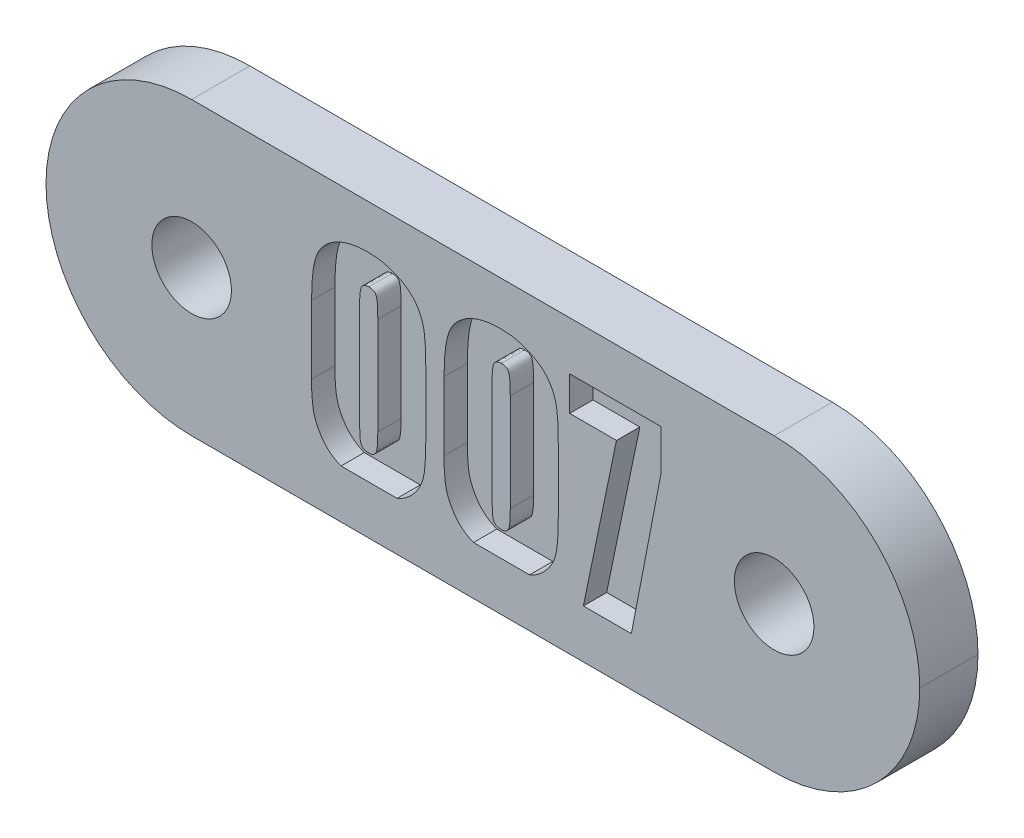
SolidWorks part; units mm, degrees
ref_plane "Front Plane" through (0, 0, 0) normal (0, 0, 1) x (1, 0, 0)
ref_plane "Top Plane" through (0, 0, 0) normal (0, 1, 0) x (1, 0, 0)
ref_plane "Right Plane" through (0, 0, 0) normal (1, 0, 0) x (0, 0, -1)
sketch "Sketch1" plane through (0, 0, 0) normal (0, 0, 1) x (1, 0, 0)
  line L1 (-22.5, 7.5) -> (22.5, 7.5)
  line L2 (-22.5, 7.5) -> (-22.5, -7.5)
  line L3 (-22.5, -7.5) -> (22.5, -7.5)
  line L4 (22.5, 7.5) -> (22.5, -7.5)
  line L5 (-22.5, 7.5) -> (22.5, -7.5) construction
  line L6 (-22.5, -7.5) -> (22.5, 7.5) construction
  point P0 (0, 0)
  dimension "D1" = 45
  dimension "D2" = 15
extrude "Boss-Extrude1" add sketch "Sketch1" along normal blind 3
sketch "Sketch2" plane through (0, 0, 3) normal (0, 0, 1) x (1, 0, 0)
  circle A0 centre (15, 0) radius 2.05
  circle A1 centre (-15, 0) radius 2.05
  point P4 (13.7306, -0.519)
  dimension "D1" = 4.1
  dimension "D2" = 30
  dimension "D3" = 15
extrude "Cut-Extrude1" cut sketch "Sketch2" against normal blind 4
sketch "Sketch5" plane through (0, 0, 3) normal (0, 0, 1) x (1, 0, 0)
  line L0 (-11, -5) -> (11, -5)
  line L2 (-2.9412, 1.6287) -> (-2.9412, -1.7353)
  line L3 (-8.8235, -1.8897) -> (-8.8235, 1.6287)
  line L4 (-6.3529, 2.4908) -> (-6.3529, -2.4596)
  line L5 (-5.4118, -2.5349) -> (-5.4118, 2.4908)
  line L6 (3.8824, 1.6287) -> (3.8824, -1.7353)
  line L7 (-2, -1.8897) -> (-2, 1.6287)
  line L8 (0.4706, 2.4908) -> (0.4706, -2.4596)
  line L9 (1.4118, -2.5349) -> (1.4118, 2.4908)
  line L10 (9.1765, 5) -> (9.1765, 2.9118)
  line L11 (9.1765, 2.9118) -> (7.6471, -5)
  line L12 (7.6471, -5) -> (5.1765, -5)
  line L13 (5.1765, -5) -> (6.8824, 3.2353)
  line L14 (6.8824, 3.2353) -> (4.4706, 3.2353)
  line L15 (4.4706, 3.2353) -> (4.4706, 5)
  line L16 (4.4706, 5) -> (9.1765, 5)
  spline S0 degree 3 poles (-2.9412, -1.7353) (-2.9408, -1.913) (-2.9449, -2.1704) (-2.9557, -2.5002) (-2.9722, -2.7188) (-2.9863, -2.9177) (-3.0101, -3.097) (-3.0323, -3.2575) (-3.0712, -3.4455) (-3.1387, -3.6644) (-3.2499, -3.9155) (-3.3966, -4.1568) (-3.5737, -4.386) (-3.7748, -4.5972) (-4.0023, -4.7766) (-4.2476, -4.9275) (-4.515, -5.043) (-4.7995, -5.1277) (-5.2075, -5.2144) (-5.5264, -5.2336) (-5.7426, -5.2353) knots 0 0 0 0 0.102604 0.148628 0.190468 0.22916 0.263737 0.294856 0.322678 0.374488 0.426751 0.480869 0.537122 0.593665 0.648803 0.703893 0.759497 0.816458 0.875017 1 1 1 1
  spline S1 degree 3 poles (-5.7426, -5.2353) (-6.0162, -5.2337) (-6.4114, -5.2176) (-6.9066, -5.1245) (-7.2265, -5.0367) (-7.5117, -4.9165) (-7.7642, -4.7655) (-7.99, -4.5892) (-8.1798, -4.3809) (-8.3418, -4.1579) (-8.4785, -3.9256) (-8.5935, -3.6898) (-8.6671, -3.4841) (-8.7147, -3.3088) (-8.7423, -3.1586) (-8.7689, -2.9908) (-8.7878, -2.8054) (-8.8052, -2.602) (-8.8188, -2.2949) (-8.825, -2.0552) (-8.8235, -1.8897) knots 0 0 0 0 0.15504 0.222773 0.284785 0.342425 0.397312 0.450868 0.503863 0.556225 0.606593 0.65622 0.704478 0.729962 0.758931 0.790855 0.826083 0.864351 0.906358 1 1 1 1
  spline S2 degree 3 poles (-8.8235, 1.6287) (-8.8236, 1.8457) (-8.8173, 2.1609) (-8.7927, 2.5659) (-8.7667, 2.8375) (-8.7353, 3.0869) (-8.6918, 3.314) (-8.6454, 3.52) (-8.5898, 3.707) (-8.5237, 3.8797) (-8.4397, 4.0393) (-8.3439, 4.1922) (-8.2313, 4.3346) (-8.106, 4.4701) (-7.9648, 4.5951) (-7.8104, 4.7131) (-7.6413, 4.8213) (-7.4603, 4.9177) (-7.2696, 5.0033) (-7.069, 5.0745) (-6.859, 5.1334) (-6.6397, 5.1791) (-6.3295, 5.2248) (-6.0902, 5.2327) (-5.9283, 5.2353) knots 0 0 0 0 0.121111 0.175939 0.226441 0.27336 0.316156 0.35548 0.391186 0.424974 0.458474 0.491682 0.525548 0.559668 0.594546 0.630663 0.668042 0.706448 0.745028 0.784621 0.825117 0.866705 0.909558 1 1 1 1
  spline S3 degree 3 poles (-5.9283, 5.2353) (-5.6681, 5.2333) (-5.2831, 5.2052) (-4.7954, 5.0791) (-4.4626, 4.9529) (-4.162, 4.8012) (-3.8954, 4.6348) (-3.6711, 4.449) (-3.4877, 4.2451) (-3.3407, 4.0263) (-3.2152, 3.7979) (-3.12, 3.5534) (-3.0622, 3.3381) (-3.0247, 3.1521) (-3.0044, 2.9916) (-2.9837, 2.8122) (-2.9669, 2.613) (-2.9574, 2.3946) (-2.9435, 2.0645) (-2.9415, 1.807) (-2.9412, 1.6287) knots 0 0 0 0 0.143725 0.211434 0.277217 0.33964 0.396925 0.450194 0.499732 0.547635 0.595269 0.643218 0.69192 0.718101 0.747782 0.781111 0.817739 0.858008 0.901639 1 1 1 1
  spline S4 degree 3 poles (-5.4118, 2.4908) (-5.412, 2.6128) (-5.415, 2.7862) (-5.4214, 3.005) (-5.4313, 3.141) (-5.441, 3.2584) (-5.456, 3.3564) (-5.472, 3.4358) (-5.4946, 3.5156) (-5.54, 3.5969) (-5.6679, 3.6882) (-5.7898, 3.7068) (-5.8732, 3.7059) knots 0 0 0 0 0.247595 0.35216 0.444428 0.524395 0.591076 0.645728 0.688625 0.759458 0.829622 1 1 1 1
  spline S5 degree 3 poles (-5.8732, 3.7059) (-5.9555, 3.7069) (-6.0805, 3.6878) (-6.2065, 3.5881) (-6.2557, 3.504) (-6.2843, 3.4216) (-6.3011, 3.3404) (-6.3183, 3.2425) (-6.3299, 3.1263) (-6.3414, 2.9928) (-6.3512, 2.7789) (-6.3518, 2.6097) (-6.3529, 2.4908) knots 0 0 0 0 0.169513 0.24293 0.318863 0.363704 0.419819 0.486676 0.565508 0.6566 0.7587 1 1 1 1
  spline S6 degree 3 poles (-6.3529, -2.4596) (-6.3514, -2.5919) (-6.3518, -2.7796) (-6.3408, -3.0154) (-6.332, -3.1595) (-6.3214, -3.2822) (-6.3081, -3.3825) (-6.2893, -3.461) (-6.2651, -3.5367) (-6.2127, -3.608) (-6.0875, -3.6916) (-5.9673, -3.7071) (-5.886, -3.7059) knots 0 0 0 0 0.261808 0.370991 0.466926 0.547244 0.614602 0.666926 0.706792 0.771036 0.837262 1 1 1 1
  spline S7 degree 3 poles (-5.886, -3.7059) (-5.8035, -3.707) (-5.6798, -3.6878) (-5.5544, -3.5901) (-5.5069, -3.5068) (-5.4792, -3.4263) (-5.4607, -3.3475) (-5.4482, -3.2525) (-5.4313, -3.1414) (-5.4244, -3.0129) (-5.4127, -2.809) (-5.4134, -2.6476) (-5.4118, -2.5349) knots 0 0 0 0 0.174906 0.248855 0.32544 0.371707 0.427109 0.494621 0.572295 0.662349 0.763853 1 1 1 1
  spline S8 degree 3 poles (3.8824, -1.7353) (3.8827, -1.913) (3.8786, -2.1704) (3.8678, -2.5002) (3.8514, -2.7188) (3.8372, -2.9177) (3.8135, -3.097) (3.7913, -3.2575) (3.7523, -3.4455) (3.6849, -3.6644) (3.5737, -3.9155) (3.4269, -4.1568) (3.2499, -4.386) (3.0487, -4.5972) (2.8213, -4.7766) (2.5759, -4.9275) (2.3085, -5.043) (2.024, -5.1277) (1.616, -5.2144) (1.2971, -5.2336) (1.0809, -5.2353) knots 0 0 0 0 0.102604 0.148628 0.190468 0.22916 0.263737 0.294856 0.322678 0.374488 0.426751 0.480869 0.537122 0.593665 0.648803 0.703893 0.759497 0.816458 0.875017 1 1 1 1
  spline S9 degree 3 poles (1.0809, -5.2353) (0.8073, -5.2337) (0.4121, -5.2176) (-0.0831, -5.1245) (-0.403, -5.0367) (-0.6882, -4.9165) (-0.9407, -4.7655) (-1.1665, -4.5892) (-1.3563, -4.3809) (-1.5183, -4.1579) (-1.655, -3.9256) (-1.77, -3.6898) (-1.8435, -3.4841) (-1.8912, -3.3088) (-1.9188, -3.1586) (-1.9454, -2.9908) (-1.9642, -2.8054) (-1.9817, -2.602) (-1.9953, -2.2949) (-2.0015, -2.0552) (-2, -1.8897) knots 0 0 0 0 0.15504 0.222773 0.284785 0.342425 0.397312 0.450868 0.503863 0.556225 0.606593 0.65622 0.704478 0.729962 0.758931 0.790855 0.826083 0.864351 0.906358 1 1 1 1
  spline S10 degree 3 poles (-2, 1.6287) (-2.0001, 1.8457) (-1.9937, 2.1609) (-1.9692, 2.5659) (-1.9432, 2.8375) (-1.9118, 3.0869) (-1.8682, 3.314) (-1.8219, 3.52) (-1.7662, 3.707) (-1.7002, 3.8797) (-1.6162, 4.0393) (-1.5204, 4.1922) (-1.4077, 4.3346) (-1.2824, 4.4701) (-1.1413, 4.5951) (-0.9869, 4.7131) (-0.8178, 4.8213) (-0.6368, 4.9177) (-0.4461, 5.0033) (-0.2455, 5.0745) (-0.0355, 5.1334) (0.1838, 5.1791) (0.494, 5.2248) (0.7334, 5.2327) (0.8952, 5.2353) knots 0 0 0 0 0.121111 0.175939 0.226441 0.27336 0.316156 0.35548 0.391186 0.424974 0.458474 0.491682 0.525548 0.559668 0.594546 0.630663 0.668042 0.706448 0.745028 0.784621 0.825117 0.866705 0.909558 1 1 1 1
  spline S11 degree 3 poles (0.8952, 5.2353) (1.1554, 5.2333) (1.5404, 5.2052) (2.0281, 5.0791) (2.3609, 4.9529) (2.6616, 4.8012) (2.9281, 4.6348) (3.1524, 4.449) (3.3359, 4.2451) (3.4828, 4.0263) (3.6083, 3.7979) (3.7035, 3.5534) (3.7613, 3.3381) (3.7988, 3.1521) (3.8191, 2.9916) (3.8398, 2.8122) (3.8566, 2.613) (3.8661, 2.3946) (3.88, 2.0645) (3.882, 1.807) (3.8824, 1.6287) knots 0 0 0 0 0.143725 0.211434 0.277217 0.33964 0.396925 0.450194 0.499732 0.547635 0.595269 0.643218 0.69192 0.718101 0.747782 0.781111 0.817739 0.858008 0.901639 1 1 1 1
  spline S12 degree 3 poles (1.4118, 2.4908) (1.4115, 2.6128) (1.4085, 2.7862) (1.4021, 3.005) (1.3922, 3.141) (1.3825, 3.2584) (1.3676, 3.3564) (1.3515, 3.4358) (1.329, 3.5156) (1.2836, 3.5969) (1.1556, 3.6882) (1.0337, 3.7068) (0.9504, 3.7059) knots 0 0 0 0 0.247595 0.35216 0.444428 0.524395 0.591076 0.645728 0.688625 0.759458 0.829622 1 1 1 1
  spline S13 degree 3 poles (0.9504, 3.7059) (0.868, 3.7069) (0.743, 3.6878) (0.6171, 3.5881) (0.5678, 3.504) (0.5392, 3.4216) (0.5225, 3.3404) (0.5052, 3.2425) (0.4936, 3.1263) (0.4821, 2.9928) (0.4723, 2.7789) (0.4718, 2.6097) (0.4706, 2.4908) knots 0 0 0 0 0.169513 0.24293 0.318863 0.363704 0.419819 0.486676 0.565508 0.6566 0.7587 1 1 1 1
  spline S14 degree 3 poles (0.4706, -2.4596) (0.4721, -2.5919) (0.4717, -2.7796) (0.4827, -3.0154) (0.4915, -3.1595) (0.5021, -3.2822) (0.5155, -3.3825) (0.5342, -3.461) (0.5584, -3.5367) (0.6108, -3.608) (0.7361, -3.6916) (0.8562, -3.7071) (0.9375, -3.7059) knots 0 0 0 0 0.261808 0.370991 0.466926 0.547244 0.614602 0.666926 0.706792 0.771036 0.837262 1 1 1 1
  spline S15 degree 3 poles (0.9375, -3.7059) (1.02, -3.707) (1.1437, -3.6878) (1.2691, -3.5901) (1.3167, -3.5068) (1.3443, -3.4263) (1.3628, -3.3475) (1.3753, -3.2525) (1.3923, -3.1414) (1.3991, -3.0129) (1.4109, -2.809) (1.4101, -2.6476) (1.4118, -2.5349) knots 0 0 0 0 0.174906 0.248855 0.32544 0.371707 0.427109 0.494621 0.572295 0.662349 0.763853 1 1 1 1
  point P1 (0, -5)
  point P4 (0, 0)
  point P6 (0, 0)
  dimension "D1" = 5
extrude "Cut-Extrude2" cut sketch "Sketch5" against normal blind 1.2 contours S3 S2 L3 S1 L0 S0 L2 S7 S6 L4 S5 S4 L5 | S11 S10 L7 S9 L0 S8 L6 S15 S14 L8 S13 S12 L9 | L16 L15 L14 L13 L0 L11 L10 region at (7.1093, 0.5673, 3) region at (-5.8633, -4.8819, 3) region at (0.9602, -4.8819, 3)
fillet "Fillet1" radius 7.5 4 edges at (22.5, 7.5, 1.5) (22.5, -7.5, 1.5) (-22.5, -7.5, 1.5) (-22.5, 7.5, 1.5)
